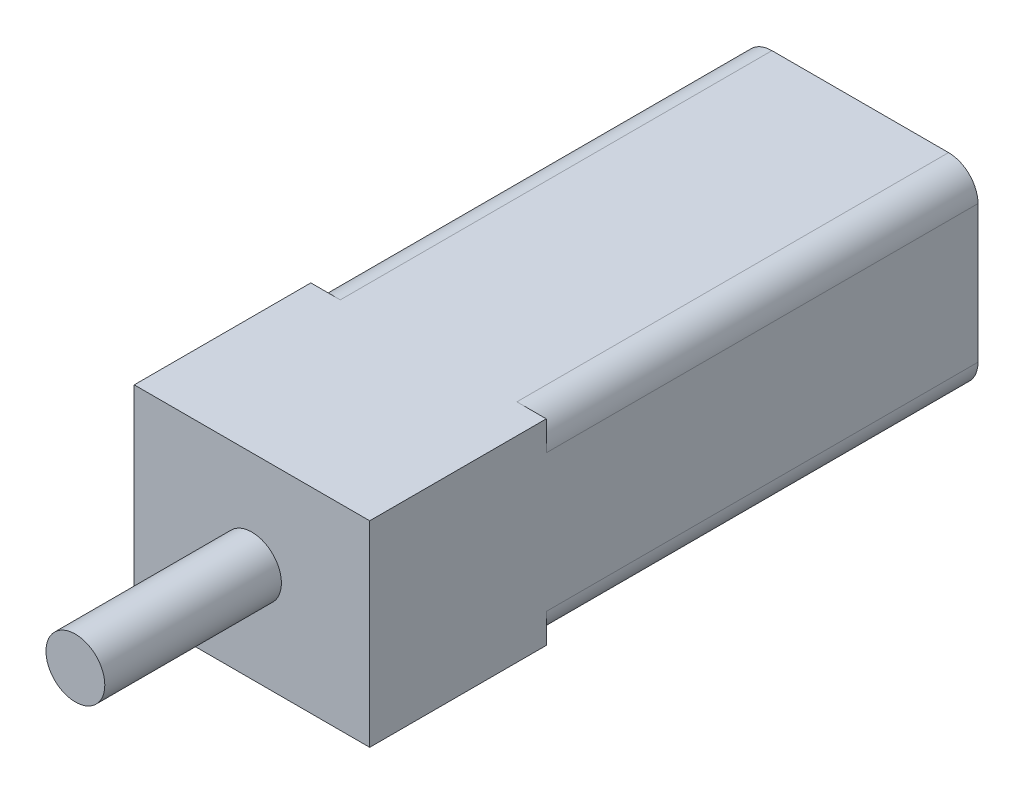
SolidWorks part; units mm, degrees
ref_plane "Front Plane" through (0, 0, 0) normal (0, 0, 1) x (1, 0, 0)
ref_plane "Top Plane" through (0, 0, 0) normal (0, 1, 0) x (1, 0, 0)
ref_plane "Right Plane" through (0, 0, 0) normal (1, 0, 0) x (0, 0, -1)
sketch "Sketch1" plane through (0, 0, 0) normal (0, 0, 1) x (1, 0, 0)
  line L1 (-6, 5) -> (6, 5)
  line L2 (-6, 5) -> (-6, -5)
  line L3 (-6, -5) -> (6, -5)
  line L4 (6, 5) -> (6, -5)
  line L5 (-6, 5) -> (6, -5) construction
  line L6 (-6, -5) -> (6, 5) construction
  point P1 (0, 0)
  dimension "D1" = 12
  dimension "D2" = 10
extrude "Boss-Extrude2" add sketch "Sketch1" along normal blind 9
sketch "Sketch2" plane through (0, 0, 9) normal (0, 0, 1) x (1, 0, 0)
  circle A0 centre (0, 0) radius 1.5
  dimension "D1" = 3
extrude "Boss-Extrude3" add sketch "Sketch2" along normal blind 9
sketch "Sketch3" plane through (0, 0, 0) normal (0, 0, -1) x (-1, 0, 0)
  line L1 (-4.5, 5) -> (4.5, 5)
  line L2 (-6, 3.5) -> (-6, -3.5)
  line L3 (-4.5, -5) -> (4.5, -5)
  line L4 (6, 3.5) -> (6, -3.5)
  arc A0 (-4.5, -5) -> (-6, -3.5) centre (-4.5, -3.5) cw
  arc A1 (6, 3.5) -> (4.5, 5) centre (4.5, 3.5) ccw
  arc A2 (6, -3.5) -> (4.5, -5) centre (4.5, -3.5) cw
  arc A3 (-4.5, 5) -> (-6, 3.5) centre (-4.5, 3.5) ccw
  point P12 (6, -5)
  point P15 (-6, 5)
  dimension "D1" = 1.5
extrude "Boss-Extrude5" add sketch "Sketch3" along normal blind 22
